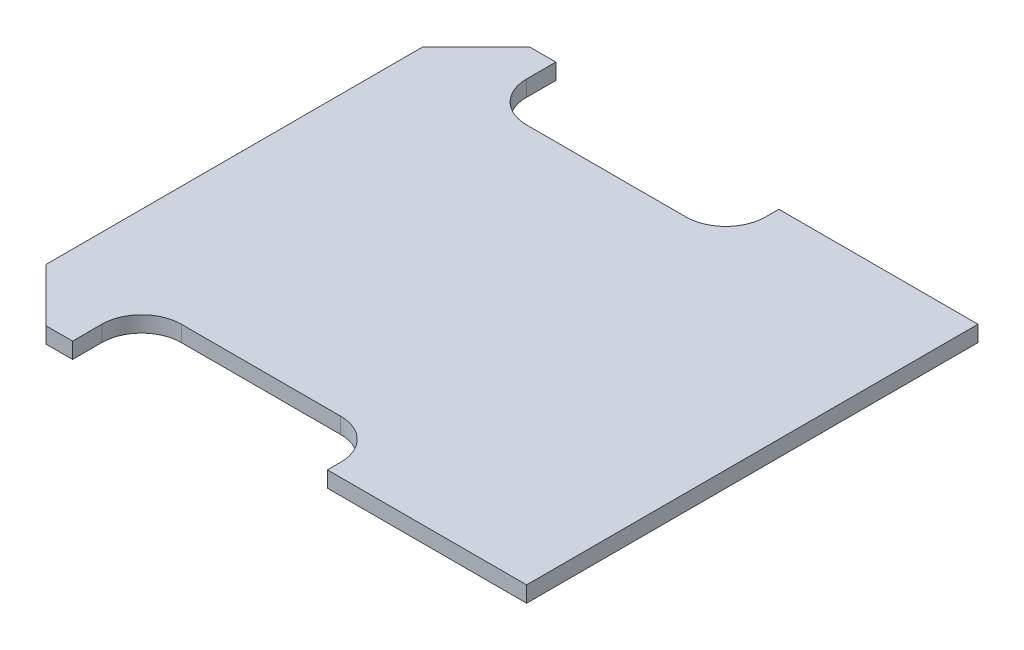
SolidWorks part; units mm, degrees
material "ABS"
ref_plane "Front Plane" through (0, 0, 0) normal (0, 0, 1) x (1, 0, 0)
ref_plane "Top Plane" through (0, 0, 0) normal (0, 1, 0) x (1, 0, 0)
ref_plane "Right Plane" through (0, 0, 0) normal (1, 0, 0) x (0, 0, -1)
sketch "Sketch1" plane through (0, 0, 0) normal (0, 1, 0) x (1, 0, 0)
  line L1 (-97.5, 85) -> (97.5, 85)
  line L2 (-97.5, 85) -> (-97.5, -85)
  line L3 (-97.5, -85) -> (97.5, -85)
  line L4 (97.5, 85) -> (97.5, -85)
  line L5 (-97.5, 85) -> (97.5, -85) construction
  line L6 (-97.5, -85) -> (97.5, 85) construction
  point P0 (0, 0)
  dimension "D1" = 195
  dimension "D2" = 170
extrude "Boss-Extrude1" add sketch "Sketch1" along normal blind 6
sketch "Sketch2" plane through (0, 6, 0) normal (0, 1, 0) x (1, 0, 0)
  line L0 (-97.5, -85) -> (-67.5, -85) construction
  line L1 (-97.5, -85) -> (97.5, -85) construction
  line L2 (0, 0) -> (-97.5, 0) construction
  line L3 (-67.5, -85) -> (22.5, -85)
  line L4 (-67.5, -85) -> (-67.5, -65)
  line L5 (-67.5, -65) -> (22.5, -65)
  line L6 (22.5, -85) -> (22.5, -65)
  line L7 (-97.5, 85) -> (-97.5, -85) construction
  line L8 (-67.5, 65) -> (22.5, 65)
  line L9 (22.5, 85) -> (22.5, 65)
  line L10 (-67.5, 85) -> (22.5, 85)
  line L11 (-67.5, 85) -> (-67.5, 65)
  dimension "D1" = 30
  dimension "D2" = 90
  dimension "D3" = 20
extrude "Cut-Extrude1" cut sketch "Sketch2" against normal through all
fillet "Fillet1" radius 15 4 edges at (22.5, 3, -65) (-67.5, 3, -65) (-67.5, 3, 65) (22.5, 3, 65)
sketch "Sketch3" plane through (0, 6, 0) normal (0, 1, 0) x (1, 0, 0)
  line L0 (0, 0) -> (-97.5, 0) construction
  line L1 (-67.5, 85) -> (-97.5, 85)
  line L2 (-67.5, 85) -> (-67.5, 91)
  line L3 (-67.5, 91) -> (-97.5, 91)
  line L4 (-97.5, 85) -> (-97.5, 91)
  line L5 (-97.5, 85) -> (-97.5, -85) construction
  line L6 (-67.5, -91) -> (-97.5, -91)
  line L7 (-97.5, -85) -> (-97.5, -91)
  line L8 (-67.5, -85) -> (-97.5, -85)
  line L9 (-67.5, -85) -> (-67.5, -91)
  dimension "D1" = 6
extrude "Boss-Extrude2" add sketch "Sketch3" against normal up to surface (6 mm away) up to face at (-16.875, 0, 0)
chamfer "Chamfer1" distance 20 angle 45 2 edges at (-97.5, 3, -91) (-97.5, 3, 91)
